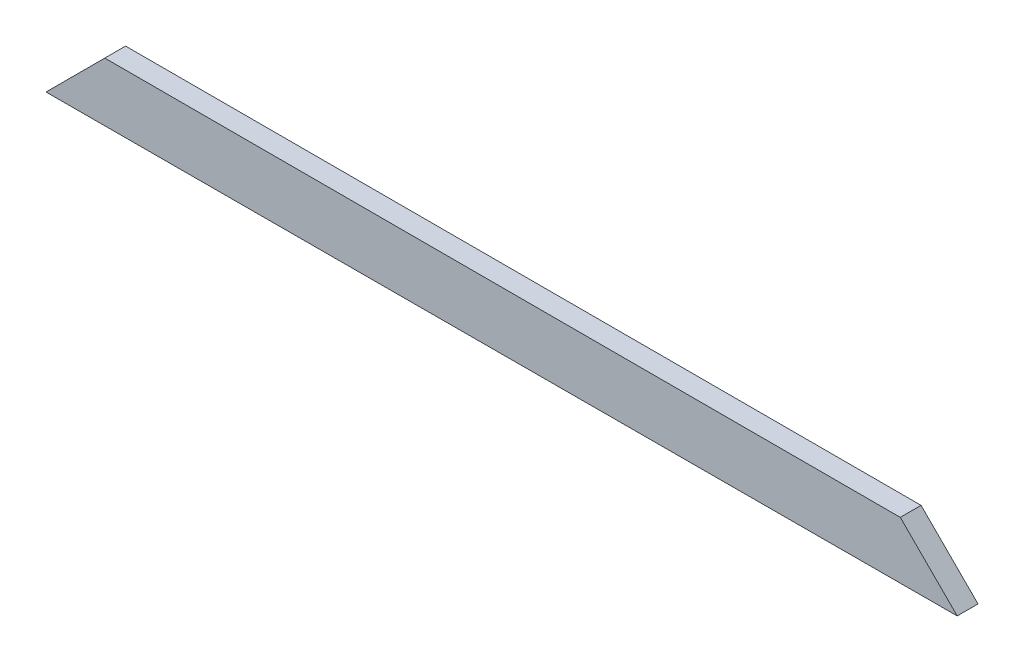
SolidWorks part; units mm, degrees
ref_plane "Front Plane" through (0, 0, 0) normal (0, 0, 1) x (1, 0, 0)
ref_plane "Top Plane" through (0, 0, 0) normal (0, 1, 0) x (1, 0, 0)
ref_plane "Right Plane" through (0, 0, 0) normal (1, 0, 0) x (0, 0, -1)
sketch "Sketch1" plane through (0, 0, 0) normal (0, 0, 1) x (1, 0, 0)
  line L0 (-139.4438, -165.8849) -> (138.8703, -165.3114)
  line L1 (0, -26.4411) -> (139.4438, -165.8849) construction
  line L2 (138.8703, -165.3114) -> (121.4833, -147.9244)
  line L3 (121.4833, -147.9244) -> (-121.4833, -147.9244)
  line L4 (-139.4438, -165.8849) -> (0, -26.4411) construction
  line L5 (-121.4833, -147.9244) -> (-139.4438, -165.8849)
  arc A0 (138.8703, -165.3114) -> (-138.8703, -165.3114) centre (0, 0) ccw construction
  dimension "D1" = 25.4
extrude "Boss-Extrude1" add sketch "Sketch1" along normal mid plane 6.35
